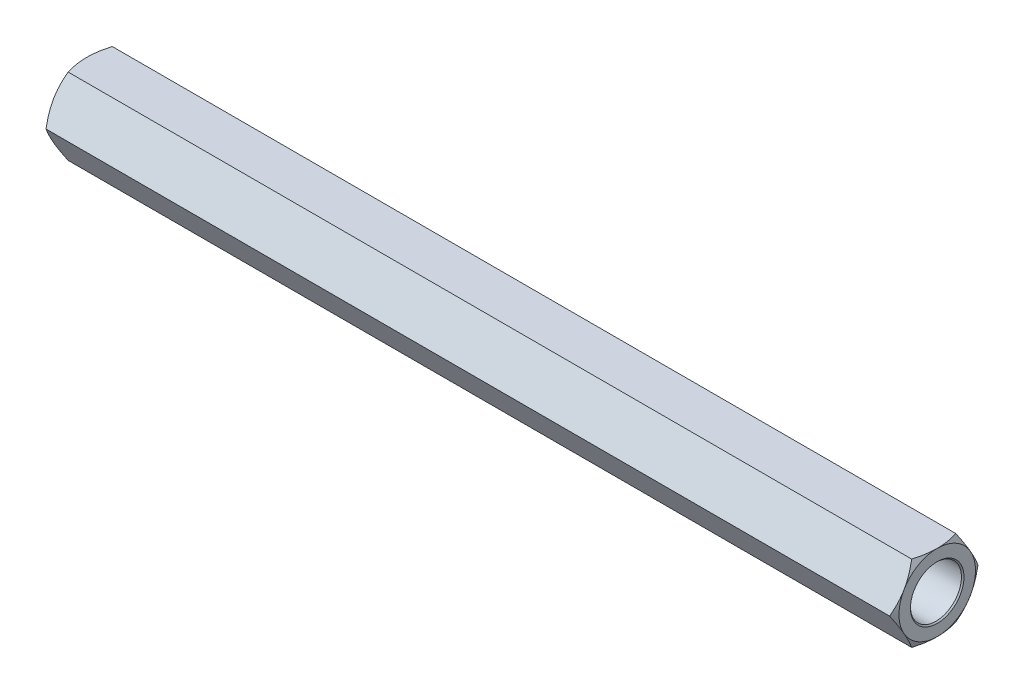
SolidWorks part; units mm, degrees
material "6061-T6 (SS)"
ref_plane "Front Plane" through (0, 0, 0) normal (0, 0, 1) x (1, 0, 0)
ref_plane "Top Plane" through (0, 0, 0) normal (0, 1, 0) x (1, 0, 0)
ref_plane "Right Plane" through (0, 0, 0) normal (1, 0, 0) x (0, 0, -1)
sketch "Sketch1" plane through (0, 0, 0) normal (0, 0, 1) x (1, 0, 0)
  line L0 (0, 0) -> (50, 0) construction
  line L1 (0, 2.25) -> (0, -2.25) construction
  line L2 (0, 1.5) -> (6.3, 1.5) construction
  line L3 (0, 1.5) -> (-0.5, 1.5) construction
  line L4 (0, 2.25) -> (50, 2.25) construction
  point P6 (0, 0)
  dimension "Hex" = 4.5
  dimension "Pitch" = 0.5
  dimension "Thread Length" = 6.3
  dimension "Thread OD" = 3
  dimension "Length" = 50
sketch "Sketch2" plane through (0, 0, 0) normal (1, 0, 0) x (0, 0, -1)
  line L0 (0, 0) -> (-1.0607, -1.0607) construction
  line L1 (1.299, 2.25) -> (-1.299, 2.25)
  line L2 (-1.299, 2.25) -> (-2.5981, 0)
  line L3 (-2.5981, 0) -> (-1.299, -2.25)
  line L4 (-1.299, -2.25) -> (1.299, -2.25)
  line L5 (1.299, -2.25) -> (2.5981, 0)
  line L6 (2.5981, 0) -> (1.299, 2.25)
  circle A0 centre (0, 0) radius 2.25 construction
  circle A1 centre (0, 0) radius 1.5 construction
  dimension "D1" = 45
extrude "Boss-Extrude1" add sketch "Sketch2" along normal up to vertex (50 mm away) up to point (50, 0, 0)
sketch "Sketch3" plane through (0, 0, 0) normal (0, 0, 1) x (1, 0, 0)
  line L0 (0, 1.575) -> (0.075, 1.5)
  line L1 (0, 0) -> (6.3, 0)
  line L2 (0, 0) -> (0, 1.575)
  line L3 (0.075, 1.5) -> (6.3, 1.5)
  line L4 (6.3, 0) -> (6.3, 1.5)
  line L5 (50, 0) -> (43.7, 0)
  line L8 (43.7, 0) -> (43.7, 1.5)
  line L9 (0, 2.25) -> (0, -2.25) construction
  line L13 (0, 0) -> (50, 0) construction
  line L14 (43.7, 1.5) -> (49.925, 1.5)
  line L15 (49.925, 1.5) -> (50, 1.575)
  line L16 (50, 2.25) -> (50, 0) construction
  line L17 (50, 1.575) -> (50, 0)
  dimension "D1" = 3.15
  dimension "D2" = 45
revolve "Cut-Revolve1" cut sketch "Sketch3" angle 360 about L13
sketch "Sketch4" plane through (0, 0, 0) normal (-1, 0, 0) x (0, 0, 1)
  circle A0 centre (0, 0) radius 2.25
  circle A1 centre (0, 0) radius 2.25 construction
extrude "Cut-Extrude1" cut sketch "Sketch4" against normal through all draft 60 flip side to cut
sketch "Sketch5" plane through (50, 0, 0) normal (1, 0, 0) x (0, 0, -1)
  circle A0 centre (0, 0) radius 2.25
  circle A1 centre (0, 0) radius 2.25 construction
extrude "Cut-Extrude2" cut sketch "Sketch5" against normal through all draft 60 flip side to cut
ref_axis "Center Axis 1" through (0, 0, 0) along (1, 0, 0)
sketch "Sketch6" [suppressed] plane through (0, 0, 0) normal (0, 0, 1) x (1, 0, 0)
  line L0 (-0.4278, 1.5) -> (-0.2139, 1.1295) construction
  line L1 (-0.2139, 1.1295) -> (0, 1.5) construction
  line L2 (0, 1.5) -> (-0.4278, 1.5) construction
  line L3 (0, 1.5) -> (-0.5, 1.5) construction
  line L5 (-0.4278, 1.5) -> (-0.4639, 1.5625) construction
  line L6 (-0.4639, 1.5625) -> (0.0361, 1.5625) construction
  line L7 (0.0361, 1.5625) -> (0, 1.5) construction
  line L8 (-0.2452, 1.1836) -> (-0.1827, 1.1836) construction
  line L9 (-0.2139, 1.5) -> (-0.2139, 1.5625) construction
  line L10 (-0.4459, 1.5312) -> (0.018, 1.5312)
  line L11 (0.018, 1.5312) -> (-0.1827, 1.1836)
  line L12 (-0.1827, 1.1836) -> (-0.2452, 1.1836)
  line L13 (-0.2452, 1.1836) -> (-0.4459, 1.5312)
  dimension "D1" = 0.0625
sketch "Sketch7" [suppressed] plane through (0, 0, 0) normal (-1, 0, 0) x (0, 0, 1)
  line L0 (0, 2.25) -> (0, -2.25) construction
  circle A0 centre (0, 0) radius 1.5
curve "Helix/Spiral1" [suppressed] pitch 0.5 height 6.8 turns 13.6
sweep "Sweep1" [suppressed] add profiles "Sketch6" path "Helix/Spiral1"
pattern_linear "LPattern1" [suppressed] count 2 spacing 43.7 along (1, 0, 0)
combine bodies "Combine1" [suppressed] operation type add bodies to combine 107 108 109
sketch "Sketch8" [suppressed] plane through (0, 0, 0) normal (-1, 0, 0) x (0, 0, 1)
  circle A0 centre (0, 0) radius 1.575
extrude "Cut-Extrude3" [suppressed] cut sketch "Sketch8" against normal through all draft 45 and the other way through all draft 45
sketch "Sketch9" [suppressed] plane through (50, 0, 0) normal (1, 0, 0) x (0, 0, -1)
  circle A0 centre (0, 0) radius 1.575
  circle A1 centre (0, 0) radius 1.575 construction
extrude "Cut-Extrude4" [suppressed] cut sketch "Sketch9" against normal through all draft 45 and the other way through all draft 45
equation "\"D1@Sketch3\"=\"Thread OD@Sketch1\"*1.05"
equation "\"D1@Sketch6\"=\"Pitch@Sketch1\"/8"
equation "\"D4@Helix/Spiral1\"=\"Pitch@Sketch1\""
equation "\"D3@Helix/Spiral1\"=\"Pitch@Sketch1\"+\"Thread Length@Sketch1\""
equation "\"D3@LPattern1\"=\"Length@Sketch1\"-\"Thread Length@Sketch1\""
equation "\"Length@Sketch1\"=\"Strut Length@Rocker Bogie Assy.Assembly\""
